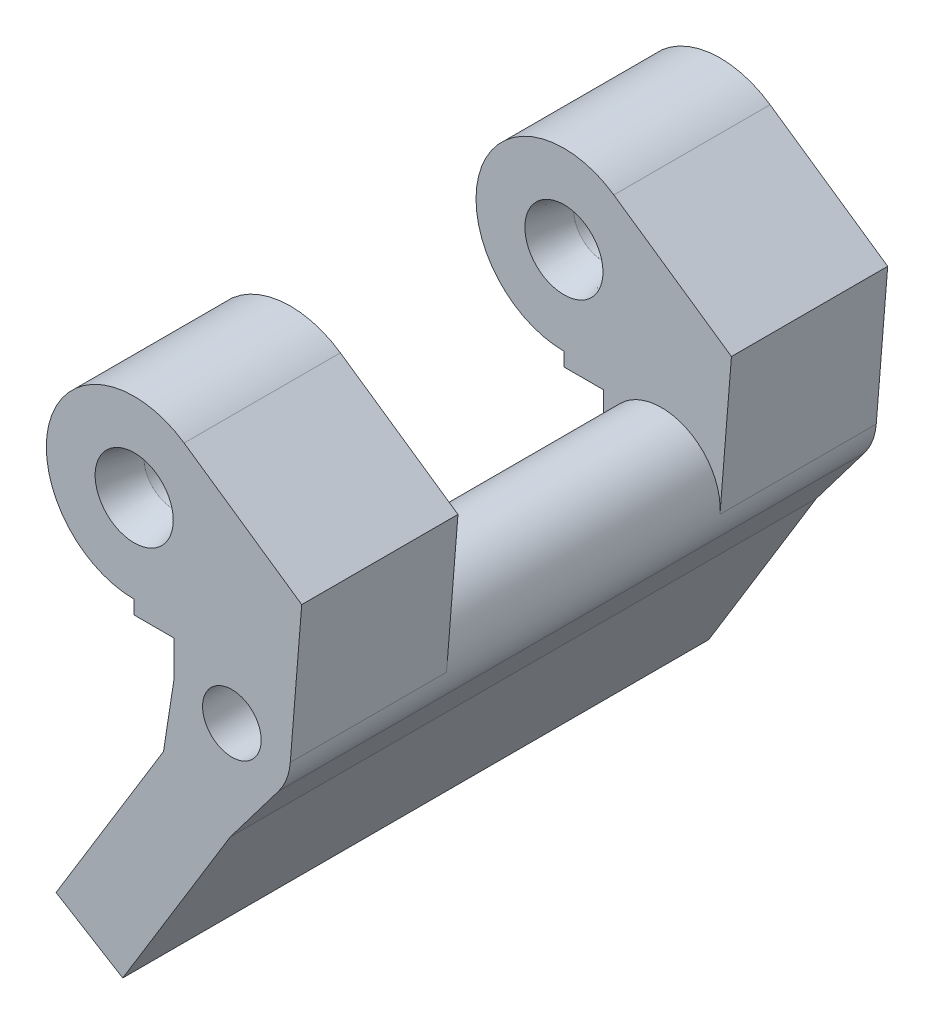
SolidWorks part; units mm, degrees
note: The reader was unsure of these and kept them because the rebuilt part matched: shared geometry of "Sketch1<5>".
ref_plane "Płaszczyzna przednia" through (0, 0, 0) normal (0, 0, 1) x (1, 0, 0)
ref_plane "Płaszczyzna górna" through (0, 0, 0) normal (0, 1, 0) x (1, 0, 0)
ref_plane "Płaszczyzna prawa" through (0, 0, 0) normal (1, 0, 0) x (0, 0, -1)
sketch "Sketch1" plane through (0, 0, 0) normal (0, 0, 1) x (1, 0, 0)
  line L0 (0, -9.4894) -> (22, -9.4894)
  line L1 (0, -13.4894) -> (22, -13.4894)
  line L2 (22, -13.4894) -> (22, -14.4894)
  line L3 (16.5, -23.4894) -> (0, -23.4894)
  line L4 (22, -14.4894) -> (16.5, -23.4894)
  line L5 (0, -13.4894) -> (0, -23.4894)
  line L16 (22, -13.4894) -> (22, -9.4894)
  line L17 (16.5, -23.4894) -> (22, -14.4894)
  line L18 (25.4131, -16.5752) -> (19.9131, -25.5752)
  line L19 (16.5, -23.4894) -> (19.9131, -25.5752)
  line L20 (22, -14.4894) -> (25.4131, -16.5752)
  line L21 (22.5353, -11.0305) -> (22, -14.4894)
  line L22 (0, 7.9714) -> (0, -34.676) construction
  line L23 (25.4131, -16.5752) -> (27.8921, -13.2998)
  line L24 (13, -9.4894) -> (13, 0.5106) construction
  line L25 (13, 0.5106) -> (22, 0.5106) construction
  line L26 (22, 0.5106) -> (22, -9.4894) construction
  line L27 (23.055, -0.2851) -> (29.0765, -4.4384)
  line L28 (29.0765, -4.4384) -> (28.4904, -11.7297)
  line L29 (20.5, -8.4894) -> (22.5353, -8.4894)
  line L30 (22.5353, -11.0305) -> (22.5353, -8.4894)
  line L31 (20.5, -8.4894) -> (20.5, -9.1894)
  line L32 (20.5, -9.1894) -> (22.5353, -9.1894)
  circle A1 centre (25.5, -11.4894) radius 3
  circle A2 centre (25.5, -11.4894) radius 1.5
  circle A3 centre (20.5, -3.9894) radius 2.05 construction
  circle A4 centre (20.5, -3.9894) radius 1.5
  circle A5 centre (20.5, -3.9894) radius 4.5
  point P4 (22, -23.4894)
  point P9 (-0.2, -13.2894)
  point P10 (22.2, -13.2894)
  point P13 (-0.2, -23.6894)
  point P14 (18.8555, -27.6894)
  point P15 (-4.2, -27.6894)
  point P16 (-4.2, -9.2894)
  point P17 (26.2, -9.2894)
  point P49 (0, 0)
  dimension "D7" = 6
  dimension "D9" = 2
  dimension "D10" = 3
  dimension "D13" = 4.1
  dimension "D14" = 3
  dimension "D18" = 9
  dimension "D1" = 9
  dimension "D2" = 5.5
  dimension "D3" = 10
  dimension "D4" = 5
  dimension "D5" = 4
  dimension "D6" = 4
  dimension "D8" = 3.5
  dimension "D11" = 10
  dimension "D12" = 13
  dimension "D15" = 5.5
  dimension "D16" = 9
  dimension "D17" = 22
  dimension "D19" = 120
  dimension "D20" = 0.7
extrude "Boss-Extrude1" add sketch "Sketch1" against normal blind 30 contours L20 L4 L19 L18 | A1 L21 L20 L23 | A1 A2
extrude "Boss-Extrude2" add sketch "Sketch1<5>" against normal blind 8 contours A5 L29 L30 A1 L28 L27 | A5 A4 | L31 L32 L30 L29
sketch "Sketch1<5>" plane through (0, 0, 0) normal (0, 0, 1) x (1, 0, 0) same geometry as "Sketch1"
pattern_linear "LPattern1" count 2 spacing 22 along (0, 0, -1) of "Boss-Extrude2"
chamfer "Chamfer1" distance 0.5 distance2 2 2 edges at (22, -3.9894, 0) (22, -3.9894, -22)
chamfer "Chamfer2" distance 2 distance2 0.5 1 edges at (22, -3.9894, -8)
chamfer "Chamfer3" distance 2 distance2 0.5 1 edges at (22, -3.9894, -30)
